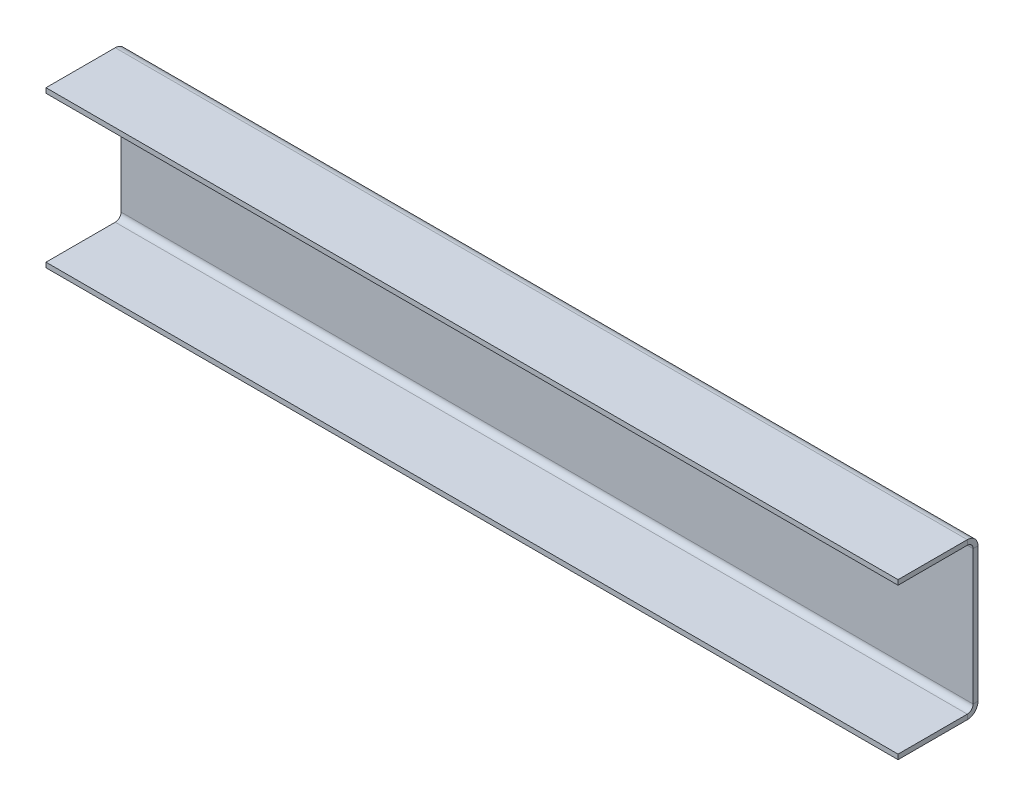
SolidWorks part; units mm, degrees
note: The reader was unsure of these and kept them because the rebuilt part matched: flange length of "Edge-Flange1".
material "ASTM A36 Steel"
ref_plane "Front Plane" through (0, 0, 0) normal (0, 0, 1) x (1, 0, 0)
ref_plane "Top Plane" through (0, 0, 0) normal (0, 1, 0) x (1, 0, 0)
ref_plane "Right Plane" through (0, 0, 0) normal (1, 0, 0) x (0, 0, -1)
sketch "Sketch1" plane through (0, 0, 0) normal (0, 0, 1) x (1, 0, 0)
  line L1 (218.5, -40) -> (-218.5, -40)
  line L2 (218.5, -40) -> (218.5, 40)
  line L3 (218.5, 40) -> (-218.5, 40)
  line L4 (-218.5, -40) -> (-218.5, 40)
  line L5 (218.5, -40) -> (-218.5, 40) construction
  line L6 (218.5, 40) -> (-218.5, -40) construction
  point P0 (0, 0)
  dimension "D1" = 80
  dimension "D2" = 437
base flange "Base-Flange1" sketch "Sketch1" thickness 2.5 reverse thickness direction no parameters "D1"=3
edge flange "Edge-Flange1" sketch "Sketch10" flange profiles "Sketch10", "Sketch11" flange angle 90 flange length 41 flange position material inside bend radius 3 thickness 2.5 relief rectangular parameters "D6"=10, "D8"=1
sketch "Sketch10" plane through (0, 40, 0) normal (0, 1, 0) x (-1, 0, 0)
  line L0 (-218.5, 0) -> (218.5, 0) construction
  line L1 (-218.5, 0) -> (218.5, 0)
  line L2 (-218.5, 0) -> (-218.5, 38.5)
  line L3 (-218.5, 38.5) -> (218.5, 38.5)
  line L4 (218.5, 38.5) -> (218.5, 0)
sketch "Sketch11" plane through (0, -40, 0) normal (0, -1, 0) x (1, 0, 0)
  line L0 (-218.5, 0) -> (218.5, 0) construction
  line L1 (-218.5, 0) -> (218.5, 0)
  line L2 (-218.5, 0) -> (-218.5, 38.5)
  line L3 (-218.5, 38.5) -> (218.5, 38.5)
  line L4 (218.5, 38.5) -> (218.5, 0)
bend "EdgeBend1" bend radius 3 bend angle 90 parameters "D5"=1
bend "EdgeBend2" bend radius 3 bend angle 90 parameters "D5"=2
sketch "Bend-Lines1" [suppressed] plane through (0, 0, 0) normal (0, 1, 0) x (1, 0, 0)
sketch "Bounding-Box1" [suppressed] plane through (0, 0, 0) normal (0, 1, 0) x (1, 0, 0)
sheet metal parameters "Sheet-Metal8" thickness 2.5 parameters "D1"=3
flat pattern "Flat-Pattern8" [suppressed]
sketch "Bend-Lines2" plane through (0, 0, 0) normal (0, 1, 0) x (1, 0, 0)
sketch3d "Bounding-Box2" [suppressed]
  line L0 (218.5, -15, 0) -> (-218.5, -15, 0) construction
  line L1 (218.5, 15, 0) -> (-218.5, 15, 0) construction
  line L2 (218.5, -15, 0) -> (218.5, 15, 0) construction
  line L3 (-218.5, -15, 0) -> (-218.5, 15, 0) construction
sheet metal parameters "Sheet-Metal9" thickness 2.5 parameters "D1"=3
flat pattern "Flat-Pattern8"
sketch "Bend-Lines2" plane through (0, 0, 0) normal (0, 0, 1) x (1, 0, 0)
  line L0 (-218.5, -37.8379) -> (218.5, -37.8379) construction
  line L1 (218.5, 37.8379) -> (-218.5, 37.8379) construction
  line L2 (-218.5, -37.8379) -> (218.5, -37.8379) construction
  line L3 (218.5, 37.8379) -> (-218.5, 37.8379) construction
sketch3d "Bounding-Box2" [suppressed]
  line L0 (-218.5, -76.6759, 0) -> (218.5, -76.6759, 0) construction
  line L1 (-218.5, 76.6759, 0) -> (218.5, 76.6759, 0) construction
  line L2 (-218.5, -76.6759, 0) -> (-218.5, 76.6759, 0) construction
  line L3 (218.5, -76.6759, 0) -> (218.5, 76.6759, 0) construction
bend of the flat pattern "Flatten-<EdgeBend1>1"
bend of the flat pattern "Flatten-<EdgeBend2>1"
